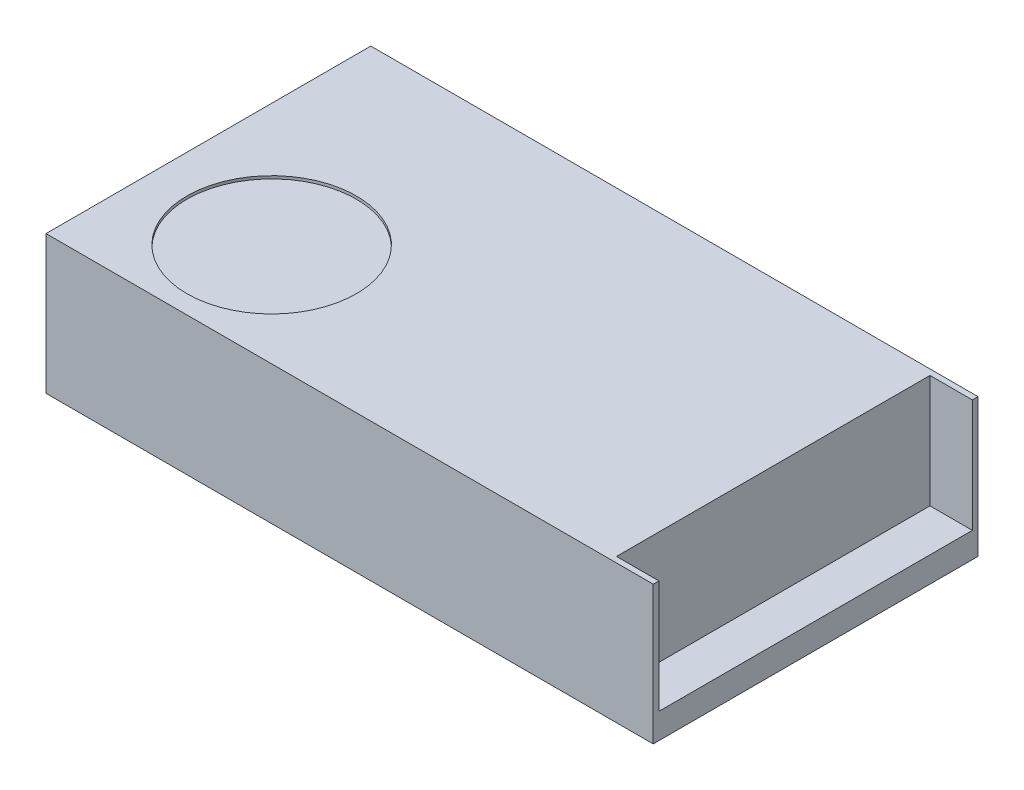
SolidWorks part; units mm, degrees
ref_plane "Front Plane" through (0, 0, 0) normal (0, 0, 1) x (1, 0, 0)
ref_plane "Top Plane" through (0, 0, 0) normal (0, 1, 0) x (1, 0, 0)
ref_plane "Right Plane" through (0, 0, 0) normal (1, 0, 0) x (0, 0, -1)
sketch "Sketch1" plane through (0, 0, 0) normal (0, 1, 0) x (1, 0, 0)
  line L1 (-107.5, -57.5) -> (107.5, -57.5)
  line L2 (-107.5, -57.5) -> (-107.5, 57.5)
  line L3 (-107.5, 57.5) -> (107.5, 57.5)
  line L4 (107.5, -57.5) -> (107.5, 57.5)
  line L5 (-107.5, -57.5) -> (107.5, 57.5) construction
  line L6 (-107.5, 57.5) -> (107.5, -57.5) construction
  point P0 (0, 0)
  dimension "D1" = 215
  dimension "D2" = 115
extrude "Boss-Extrude1" add sketch "Sketch1" along normal blind 49
sketch "Sketch2" plane through (0, 49, 0) normal (0, 1, 0) x (1, 0, 0)
  line L0 (-107.5, -57.5) -> (107.5, -57.5) construction
  line L1 (-107.5, 57.5) -> (-107.5, -57.5) construction
  circle A0 centre (-64.1, -21) radius 30
  dimension "D1" = 60
  dimension "D2" = 36.5
  dimension "D3" = 43.4
extrude "Cut-Extrude1" cut sketch "Sketch2" against normal blind 1
sketch "Sketch4" plane through (0, 49, 0) normal (0, 1, 0) x (1, 0, 0)
  line L0 (107.5, -57.5) -> (107.5, 57.5) construction
  line L1 (107.5, 55.5) -> (92.5, 55.5)
  line L2 (107.5, 55.5) -> (107.5, -55.5)
  line L3 (107.5, -55.5) -> (92.5, -55.5)
  line L4 (92.5, 55.5) -> (92.5, -55.5)
  line L5 (107.5, 57.5) -> (-107.5, 57.5) construction
  line L6 (-107.5, -57.5) -> (107.5, -57.5) construction
  dimension "D1" = 2
  dimension "D2" = 2
  dimension "D3" = 15
extrude "Cut-Extrude2" cut sketch "Sketch4" against normal blind 40
equation "\"D2@Sketch4\"=\"D1@Sketch4\""
